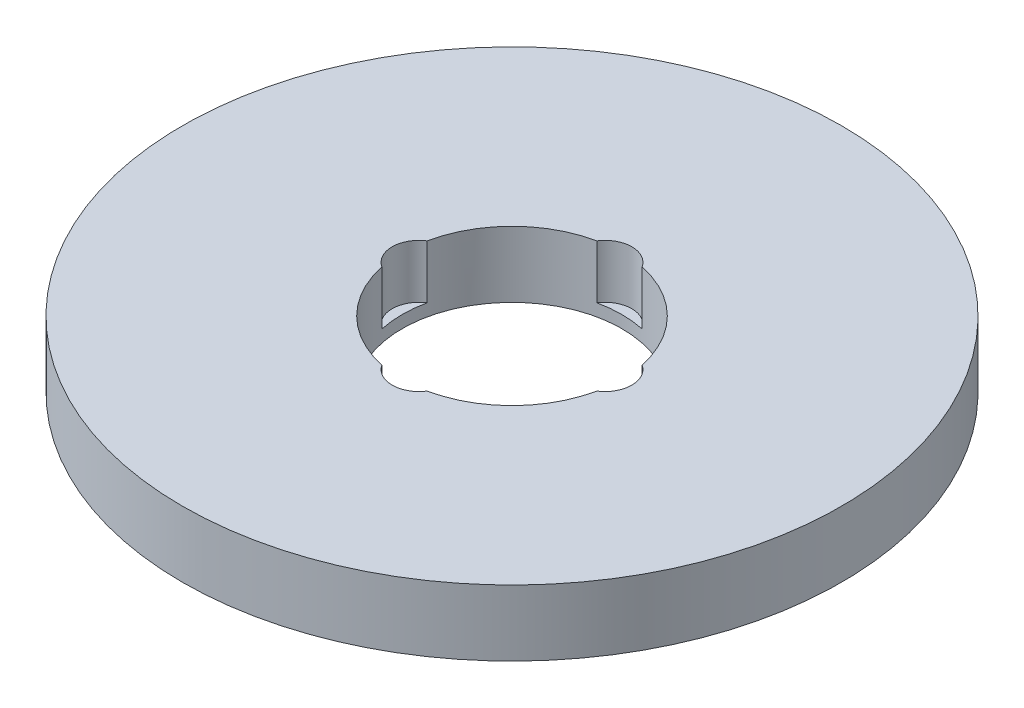
SolidWorks part; units mm, degrees
ref_plane "Front Plane" through (0, 0, 0) normal (0, 0, 1) x (1, 0, 0)
ref_plane "Top Plane" through (0, 0, 0) normal (0, 1, 0) x (1, 0, 0)
ref_plane "Right Plane" through (0, 0, 0) normal (1, 0, 0) x (0, 0, -1)
sketch "Sketch1" plane through (0, 0, 0) normal (0, 1, 0) x (1, 0, 0)
  circle A0 centre (0, 0) radius 45
  dimension "FLANGE_OD" = 90
extrude "Boss-Extrude1" add sketch "Sketch1" along normal blind 9
sketch "Sketch2" plane through (0, 0, 0) normal (0, 1, 0) x (1, 0, 0)
  circle A0 centre (0, 0) radius 15
  dimension "BORE_D" = 30
extrude "Cut-Extrude1" cut sketch "Sketch2" along normal through all
sketch "Sketch3" plane through (0, 9, 0) normal (0, 1, 0) x (1, 0, 0)
  circle A0 centre (0, 0) radius 12.6965 construction
  circle A1 centre (-12.6965, 0) radius 3.6687
  dimension "BOLT_D" = 7.3373
  dimension "BOLT_PCD" = 25.393
extrude "Cut-Extrude2" cut sketch "Sketch3" against normal blind 7.3298
pattern_circular "CirPattern1" count 4 over 360 about axis through (0, 0, 0) along (0, 1, 0) of "Cut-Extrude2"
